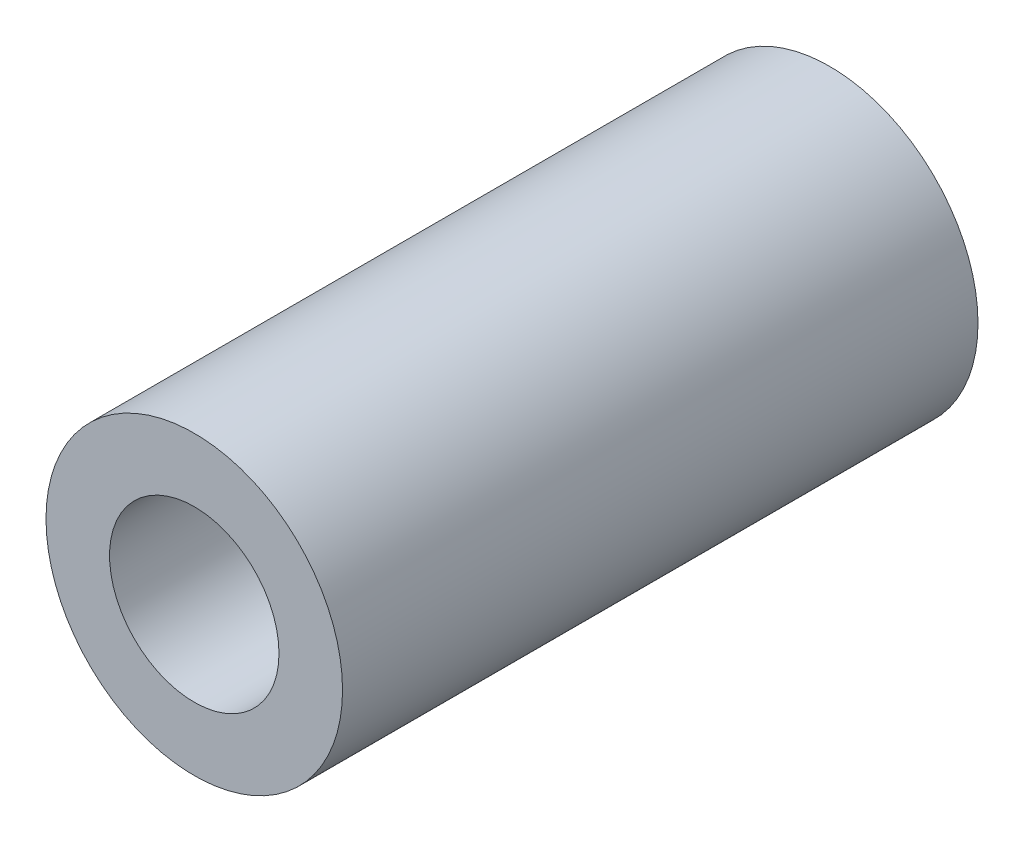
SolidWorks part; units mm, degrees
ref_plane "Piano frontale" through (0, 0, 0) normal (0, 0, 1) x (1, 0, 0)
ref_plane "Piano superiore" through (0, 0, 0) normal (0, 1, 0) x (1, 0, 0)
ref_plane "Piano destro" through (0, 0, 0) normal (1, 0, 0) x (0, 0, -1)
sketch "Schizzo1" plane through (0, 0, 0) normal (0, 0, 1) x (1, 0, 0)
  circle A0 centre (0, 0) radius 3.5
extrude "Estrusione-Estrusione1" add sketch "Schizzo1" along normal blind 15
sketch "Schizzo2" plane through (0, 0, 15) normal (0, 0, 1) x (1, 0, 0)
  circle A0 centre (0, 0) radius 2
extrude "Taglio-Estrusione1" cut sketch "Schizzo2" against normal through all
sketch "Schizzo3" plane through (0, 0, 0) normal (0, 0, -1) x (-1, 0, 0)
  circle A0 centre (0, 0) radius 1.3
  circle A1 centre (0, 0) radius 2
extrude "Estrusione-Estrusione2" add sketch "Schizzo3" against normal blind 2 separate body
chamfer "Smusso1" distance 2 angle 30 1 edges at (-1.3, 0, 0) first distance on face at (-1.3, 0, 0)
chamfer "Smusso2" distance 1 angle 30 1 edges at (2, 0, 0) first distance on face at (2, 0, 0)
